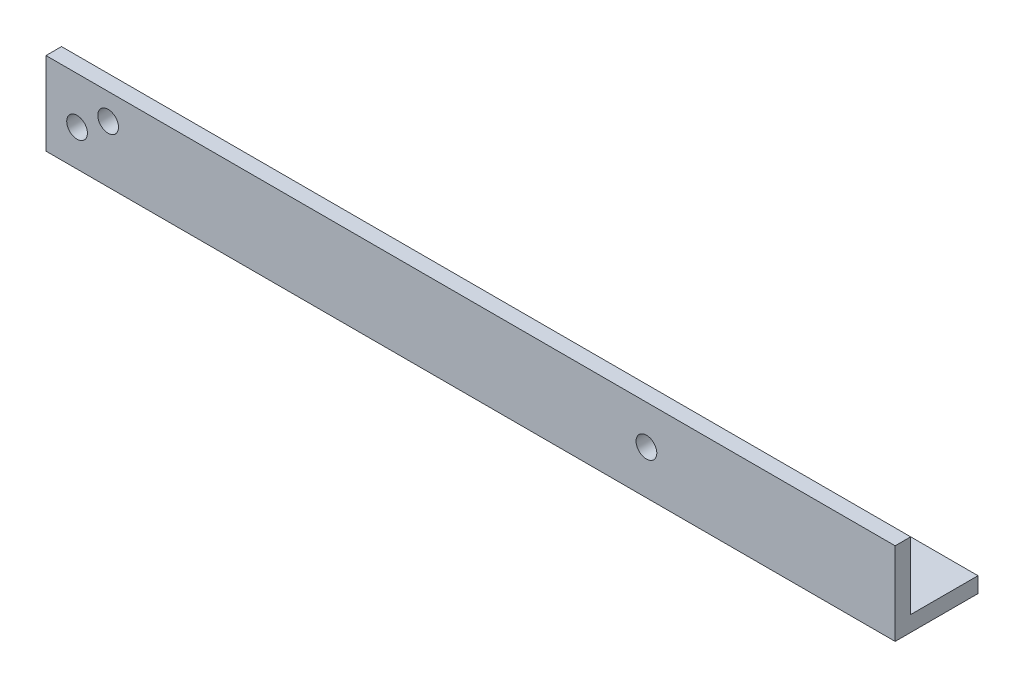
SolidWorks part; units mm, degrees
material "6061 Alloy"
ref_plane "Front Plane" through (0, 0, 0) normal (0, 0, 1) x (1, 0, 0)
ref_plane "Top Plane" through (0, 0, 0) normal (0, 1, 0) x (1, 0, 0)
ref_plane "Right Plane" through (0, 0, 0) normal (1, 0, 0) x (0, 0, -1)
sketch "Sketch1" plane through (0, 0, 0) normal (1, 0, 0) x (0, 0, -1)
  line L0 (0, 0) -> (0, -25.4)
  line L1 (0, -25.4) -> (25.4, -25.4)
  line L2 (25.4, -25.4) -> (25.4, -20.6375)
  line L3 (25.4, -20.6375) -> (4.7625, -20.6375)
  line L4 (4.7625, -20.6375) -> (4.7625, 0)
  line L5 (4.7625, 0) -> (0, 0)
  dimension "D1" = 4.7625
  dimension "D2" = 4.7625
  dimension "D3" = 25.4
  dimension "D4" = 25.4
extrude "Boss-Extrude1" add sketch "Sketch1" along normal blind 260.35
sketch "Sketch3" plane through (0, 0, -4.7625) normal (0, 0, -1) x (-1, 0, 0)
  line L0 (0, -20.6375) -> (0, 0) construction
  line L1 (-260.35, -25.4) -> (0, -25.4) construction
  circle A0 centre (-9.525, -14.2875) radius 3.175
  circle A1 centre (-19.05, -7.9375) radius 3.175
  dimension "D1" = 6.35
  dimension "D2" = 6.35
  dimension "D3" = 9.525
  dimension "D4" = 19.05
  dimension "D5" = 11.1125
  dimension "D6" = 17.4625
extrude "Cut-Extrude1" cut sketch "Sketch3" against normal up to next
sketch "Sketch4" plane through (0, 0, 0) normal (0, 0, 1) x (1, 0, 0)
  circle A0 centre (184.0953, -11.9296) radius 3.175 construction
  circle A1 centre (184.0953, -11.9296) radius 3.175
extrude "Cut-Extrude2" cut sketch "Sketch4" against normal up to next
sketch "Sketch5" plane through (0, -25.4, 0) normal (0, -1, 0) x (1, 0, 0)
  circle A0 centre (222.25, -12.7) radius 3.175 construction
  circle A1 centre (247.65, -12.7) radius 3.175 construction
  circle A2 centre (222.25, -12.7) radius 3.175
  circle A3 centre (247.65, -12.7) radius 3.175
extrude "Cut-Extrude4" cut sketch "Sketch5" against normal up to next
